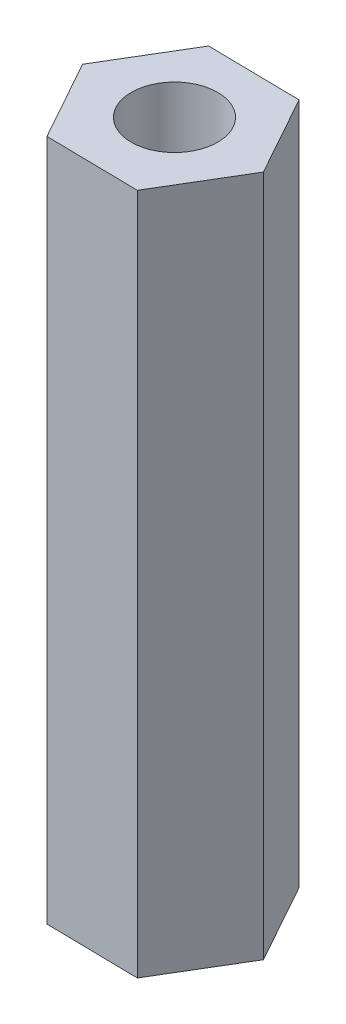
SolidWorks part; units mm, degrees
ref_plane "Front Plane" through (0, 0, 0) normal (0, 0, 1) x (1, 0, 0)
ref_plane "Top Plane" through (0, 0, 0) normal (0, 1, 0) x (1, 0, 0)
ref_plane "Right Plane" through (0, 0, 0) normal (1, 0, 0) x (0, 0, -1)
sketch "Sketch1" plane through (0, 0, 0) normal (0, 1, 0) x (1, 0, 0)
  line L1 (1.9642, -3.5321) -> (4.0409, -0.065)
  line L2 (4.0409, -0.065) -> (2.0768, 3.467)
  line L3 (2.0768, 3.467) -> (-1.9642, 3.5321)
  line L4 (-1.9642, 3.5321) -> (-4.0409, 0.065)
  line L5 (-4.0409, 0.065) -> (-2.0768, -3.467)
  line L6 (-2.0768, -3.467) -> (1.9642, -3.5321)
  circle A0 centre (0, 0) radius 3.5 construction
  circle A1 centre (0, 0.065) radius 1.9
extrude "Boss-Extrude1" add sketch "Sketch1" along normal blind 30
